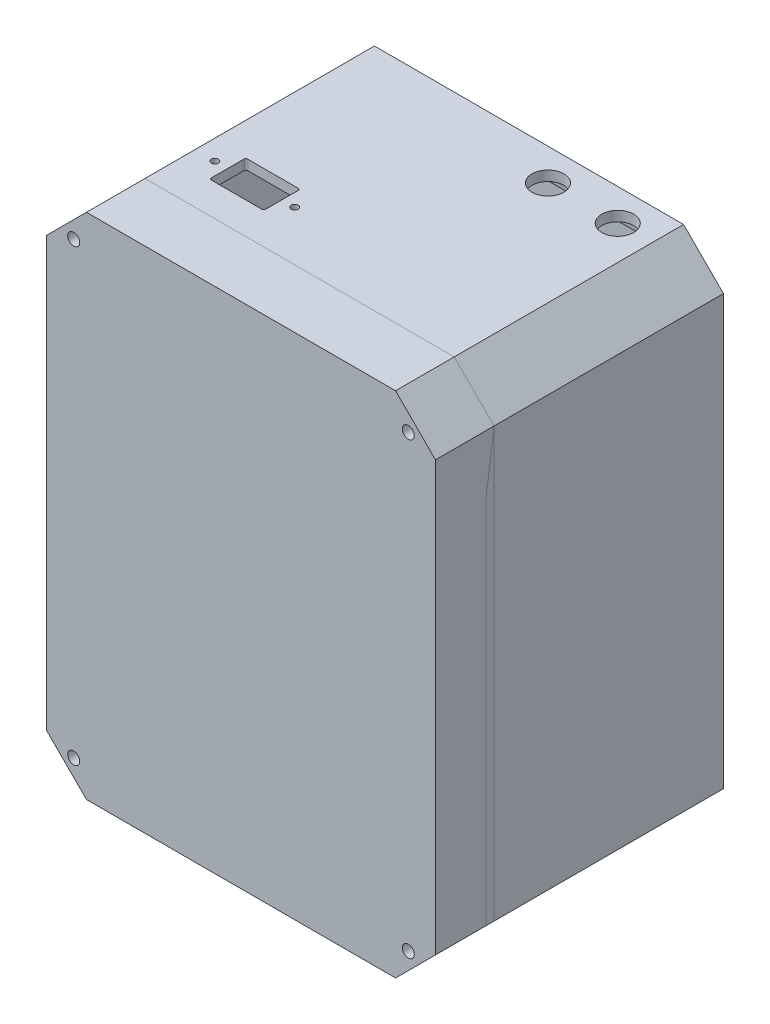
SolidWorks part; units mm, degrees
ref_plane "Front Plane" through (0, 0, 0) normal (1, 0, 0) x (0, 1, 0)
ref_plane "Top Plane" through (0, 0, 0) normal (0, 0, 1) x (0, 1, 0)
ref_plane "Right Plane" through (0, 0, 0) normal (0, 1, 0) x (-1, 0, 0)
sketch "Sketch1" plane through (0, 0, 0) normal (0, 0, 1) x (0, 1, 0)
  line L0 (-127.5, -25.5) -> (127.5, -25.5) construction
  line L1 (-107.5, 97.5) -> (107.5, 97.5)
  line L2 (-127.5, 77.5) -> (-127.5, -77.5)
  line L3 (-107.5, -97.5) -> (107.5, -97.5)
  line L4 (127.5, 77.5) -> (127.5, -77.5)
  line L5 (-127.5, 97.5) -> (127.5, -97.5) construction
  line L6 (-127.5, -97.5) -> (127.5, 97.5) construction
  line L7 (-127.5, -60.5) -> (127.5, -60.5) construction
  line L8 (-107.5, -18.875) -> (-107.5, -32.125) construction
  line L9 (-67.5, -53.875) -> (-67.5, -67.125) construction
  line L10 (-107.5, 97.5) -> (-127.5, 77.5)
  line L11 (107.5, 97.5) -> (127.5, 77.5)
  line L12 (127.5, -77.5) -> (107.5, -97.5)
  line L13 (-127.5, -77.5) -> (-107.5, -97.5)
  line L14 (-117.5, 87.5) -> (117.5, -87.5) construction
  line L15 (-112.6365, 83.8782) -> (112.6365, 83.8782) construction
  line L16 (-112.6365, 83.8782) -> (-112.6365, -83.8782) construction
  line L17 (-112.6365, -83.8782) -> (112.6365, -83.8782) construction
  line L18 (112.6365, 83.8782) -> (112.6365, -83.8782) construction
  line L19 (-112.6365, 83.8782) -> (112.6365, -83.8782) construction
  line L20 (-112.6365, -83.8782) -> (112.6365, 83.8782) construction
  circle A0 centre (-114.5, 44.5) radius 2.75 construction
  circle A1 centre (114.5, 44.5) radius 2.75 construction
  circle A2 centre (-107.5, -18.875) radius 2.75 construction
  circle A3 centre (-107.5, -32.125) radius 2.75 construction
  circle A4 centre (-67.5, -53.875) radius 2.75 construction
  circle A5 centre (-67.5, -67.125) radius 2.75 construction
  circle A6 centre (-112.6365, 83.8782) radius 2.1
  circle A7 centre (112.6365, 83.8782) radius 2.1
  circle A8 centre (112.6365, -83.8782) radius 2.1
  circle A9 centre (-112.6365, -83.8782) radius 2.1
  point P0 (0, 0)
  point P18 (-107.5, -25.5)
  point P19 (-67.5, -60.5)
  point P32 (0, 0)
  point P37 (-117.5, 87.5)
  point P41 (117.5, -87.5)
  dimension "D6" = 5.5
  dimension "D9" = 5.5
  dimension "D15" = 4.2
  dimension "D1" = 255
  dimension "D2" = 195
  dimension "D3" = 53
  dimension "D4" = 13
  dimension "D5" = 13
  dimension "D7" = 70
  dimension "D8" = 35
  dimension "D10" = 13.25
  dimension "D11" = 13.25
  dimension "D12" = 20
  dimension "D13" = 60
  dimension "D14" = 6
extrude "Boss-Extrude2" add sketch "Sketch1" along normal blind 115
shell "Shell1" thickness 5 removed face at (85.9782, 112.6365, 115)
sketch "Sketch9" plane through (0, 0, 5) normal (0, 0, 1) x (1, 0, 0)
  line L0 (-75.4289, -122.5) -> (75.4289, -122.5) construction
  line L1 (10.875, -122.5) -> (75.125, -122.5)
  line L2 (10.875, -122.5) -> (10.875, -22.5)
  line L3 (10.875, -22.5) -> (75.125, -22.5)
  line L4 (75.125, -122.5) -> (75.125, -22.5)
  dimension "D1" = 8
  dimension "D2" = 8
  dimension "D3" = 100
extrude "Boss-Extrude3" add sketch "Sketch9" along normal blind 2
sketch "Sketch10" plane through (0, 0, 5) normal (0, 0, 1) x (1, 0, 0)
  line L0 (75.125, -122.5) -> (75.125, -22.5) construction
  line L1 (10.875, -22.5) -> (75.125, -22.5)
  line L2 (10.875, -22.5) -> (10.875, 77.5)
  line L3 (10.875, 77.5) -> (75.125, 77.5)
  line L4 (75.125, -22.5) -> (75.125, 77.5)
  dimension "D1" = 100
extrude "Boss-Extrude4" add sketch "Sketch10" along normal blind 1
sketch "Sketch2" plane through (0, 0, 5) normal (0, 0, 1) x (1, 0, 0)
  circle A0 centre (53.875, -67.5) radius 2.75 construction
  circle A1 centre (67.125, -67.5) radius 2.75 construction
  circle A2 centre (32.125, -107.5) radius 2.75 construction
  circle A3 centre (18.875, -107.5) radius 2.75 construction
  circle A4 centre (-44.5, 114.5) radius 2.75 construction
  circle A5 centre (-44.5, -114.5) radius 2.75 construction
  circle A6 centre (53.875, -67.5) radius 2.75
  circle A7 centre (67.125, -67.5) radius 2.75
  circle A8 centre (32.125, -107.5) radius 2.75
  circle A9 centre (18.875, -107.5) radius 2.75
  circle A10 centre (-44.5, 114.5) radius 2.75
  circle A11 centre (-44.5, -114.5) radius 2.75
extrude "Cut-Extrude1" cut sketch "Sketch2" against normal through all both and the other way through all
sketch "Sketch3" plane through (0, -127.5, 0) normal (0, -1, 0) x (1, 0, 0)
  line L0 (-77.5, 0) -> (77.5, 0) construction
  line L1 (10.5, 0) -> (40.5, 0)
  line L2 (10.5, 0) -> (10.5, 65)
  line L3 (10.5, 65) -> (40.5, 65)
  line L4 (40.5, 0) -> (40.5, 65)
  line L6 (45.5, 0) -> (75.5, 0)
  line L7 (45.5, 0) -> (45.5, 65)
  line L8 (45.5, 65) -> (75.5, 65)
  line L9 (75.5, 0) -> (75.5, 65)
  point P10 (25.5, 0)
  point P11 (0, 0)
  point P13 (60.5, 0)
  point P14 (0, 0)
  dimension "D1" = 65
  dimension "D2" = 0
  dimension "D3" = 30
extrude "Cut-Extrude2" cut sketch "Sketch3" against normal up to surface (5 mm away) up to face at (21.5, -122.5, 33)
sketch "Sketch4" plane through (0, 127.5, 0) normal (0, 1, 0) x (-1, 0, 0)
  line L0 (-75.4289, 5) -> (75.4289, 5) construction
  circle A0 centre (-60.5, 16) radius 8
  circle A1 centre (-25.5, 16) radius 8
  point P4 (0, 0)
  point P6 (0, 0)
  point P8 (0, 0)
  dimension "D1" = 16
  dimension "D2" = 11
extrude "Cut-Extrude3" cut sketch "Sketch4" against normal up to next
chamfer "Chamfer2" distance 5 angle 45 4 edges at (-32.4645, -122.5, 5) (92.5, 0, 5) (0, 122.5, 5) (-92.5, 0, 5)
sketch "Sketch5" plane through (0, 127.5, 0) normal (0, 1, 0) x (-1, 0, 0)
  line L0 (27.5, 90) -> (67.5, 90) construction
  line L1 (34.9, 99.1) -> (60.1, 99.1)
  line L2 (33.9, 98.1) -> (33.9, 81.9)
  line L3 (34.9, 80.9) -> (60.1, 80.9)
  line L4 (61.1, 98.1) -> (61.1, 81.9)
  line L5 (33.9, 99.1) -> (61.1, 80.9) construction
  line L6 (33.9, 80.9) -> (61.1, 99.1) construction
  line L7 (-77.5, 115) -> (77.5, 115) construction
  line L8 (97.5, 115) -> (97.5, 0) construction
  circle A0 centre (27.5, 90) radius 1.75
  circle A1 centre (67.5, 90) radius 1.75
  arc A2 (33.9, 81.9) -> (34.9, 80.9) centre (34.9, 81.9) ccw
  arc A3 (60.1, 80.9) -> (61.1, 81.9) centre (60.1, 81.9) ccw
  arc A4 (61.1, 98.1) -> (60.1, 99.1) centre (60.1, 98.1) ccw
  arc A5 (34.9, 99.1) -> (33.9, 98.1) centre (34.9, 98.1) ccw
  point P0 (47.5, 90)
  point P7 (47.5, 90)
  dimension "D4" = 3.5
  dimension "D5" = 1
  dimension "D1" = 27.2
  dimension "D2" = 18.2
  dimension "D3" = 40
  dimension "D6" = 25
  dimension "D7" = 50
extrude "Cut-Extrude4" cut sketch "Sketch5" against normal up to next
sketch "Sketch6" plane through (0, 0, 5) normal (0, 0, 1) x (1, 0, 0)
  line L0 (10.5, -122.5) -> (-75.4289, -122.5) construction
  line L1 (-62, -122.5) -> (-27, -122.5)
  line L2 (-62, -122.5) -> (-62, 122.5)
  line L3 (-62, 122.5) -> (-27, 122.5)
  line L4 (-27, -122.5) -> (-27, 122.5)
  line L5 (75.4289, 122.5) -> (-75.4289, 122.5) construction
  point P8 (-44.5, -122.5)
  point P9 (-44.5, 122.5)
  point P10 (0, 0)
  dimension "D1" = 180
  dimension "D2" = 35
extrude "Cut-Extrude5" cut sketch "Sketch6" along normal through all
sketch "Sketch7" plane through (0, 122.5, 0) normal (0, -1, 0) x (1, 0, 0)
  line L0 (77.5, 0) -> (-77.5, 0) construction
  line L1 (-27, 5) -> (-62, 5) construction
  line L2 (25.5, 5) -> (35.0263, 10.5)
  line L3 (35.0263, 10.5) -> (35.0263, 21.5)
  line L4 (35.0263, 21.5) -> (25.5, 27)
  line L5 (25.5, 27) -> (15.9737, 21.5)
  line L6 (15.9737, 21.5) -> (15.9737, 10.5)
  line L7 (15.9737, 10.5) -> (25.5, 5)
  line L8 (60.5, 5) -> (70.0263, 10.5)
  line L9 (70.0263, 10.5) -> (70.0263, 21.5)
  line L10 (70.0263, 21.5) -> (60.5, 27)
  line L11 (60.5, 27) -> (50.9737, 21.5)
  line L12 (50.9737, 21.5) -> (50.9737, 10.5)
  line L13 (50.9737, 10.5) -> (60.5, 5)
  circle A2 centre (25.5, 16) radius 9.5263 construction
  circle A3 centre (60.5, 16) radius 9.5263 construction
  point P2 (0, 0)
  point P5 (0, 0)
  point P22 (0, 0)
  point P23 (0, 0)
  dimension "D1" = 0
extrude "Cut-Extrude6" cut sketch "Sketch7" along normal up to next
sketch "Sketch11" plane through (0, 0, 115) normal (0, 0, 1) x (1, 0, 0)
  line L8 (-97.5, -107.5) -> (-77.5, -127.5)
  line L9 (-77.5, -127.5) -> (77.5, -127.5)
  line L10 (77.5, -127.5) -> (97.5, -107.5)
  line L11 (97.5, -107.5) -> (97.5, 107.5)
  line L12 (97.5, 107.5) -> (77.5, 127.5)
  line L13 (77.5, 127.5) -> (-77.5, 127.5)
  line L14 (-77.5, 127.5) -> (-97.5, 107.5)
  line L15 (-97.5, 107.5) -> (-97.5, -107.5)
  line L16 (-97.5, -107.5) -> (-77.5, -127.5)
  line L17 (-77.5, -127.5) -> (77.5, -127.5)
  line L18 (77.5, -127.5) -> (97.5, -107.5)
  line L19 (97.5, -107.5) -> (97.5, 107.5)
  line L20 (97.5, 107.5) -> (77.5, 127.5)
  line L21 (77.5, 127.5) -> (-77.5, 127.5)
  line L22 (-77.5, 127.5) -> (-97.5, 107.5)
  line L23 (-97.5, 107.5) -> (-97.5, -107.5)
  circle A0 centre (83.8782, 112.6365) radius 2.75
  circle A1 centre (83.8782, -112.6365) radius 2.75
  circle A2 centre (-83.8782, -112.6365) radius 2.75
  circle A3 centre (-83.8782, 112.6365) radius 2.75
  dimension "D2" = 5.5
  dimension "D1" = 0
extrude "Boss-Extrude5" add sketch "Sketch11" along normal blind 4 separate body
sketch "Sketch12" plane through (0, 0, 115) normal (0, 0, -1) x (1, 0, 0)
  line L0 (-88.5, 102.5444) -> (-88.5, 102.5444)
  line L1 (-88.5, 102.5444) -> (-88.5, -102.5444)
  line L2 (-88.5, -102.5444) -> (-88.5, -102.5444)
  line L3 (-74.2001, -118.0719) -> (-73.7721, -118.5)
  line L4 (-73.7721, -118.5) -> (73.7721, -118.5)
  line L5 (73.7721, -118.5) -> (74.2001, -118.0719)
  line L6 (88.5, -102.5444) -> (88.5, -102.5444)
  line L7 (88.5, -102.5444) -> (88.5, 102.5444)
  line L40 (88.5, 102.5444) -> (88.5, 102.5444)
  line L41 (74.2001, 118.0719) -> (73.7721, 118.5)
  line L42 (73.7721, 118.5) -> (-73.7721, 118.5)
  line L43 (-73.7721, 118.5) -> (-74.2001, 118.0719)
  line L44 (-89.5558, 108.3732) -> (-92.5, 105.4289)
  line L45 (-92.5, 105.4289) -> (-92.5, -105.4289)
  line L46 (-92.5, -105.4289) -> (-89.5558, -108.3732)
  line L47 (-79.6149, -118.314) -> (-75.4289, -122.5)
  line L48 (-75.4289, -122.5) -> (75.4289, -122.5)
  line L49 (75.4289, -122.5) -> (79.6149, -118.314)
  line L50 (89.5558, -108.3732) -> (92.5, -105.4289)
  line L51 (92.5, -105.4289) -> (92.5, 105.4289)
  line L52 (92.5, 105.4289) -> (89.5558, 108.3732)
  line L53 (79.6149, 118.314) -> (75.4289, 122.5)
  line L54 (75.4289, 122.5) -> (-75.4289, 122.5)
  line L55 (-75.4289, 122.5) -> (-79.6149, 118.314)
  line L56 (-89.5558, 108.3732) -> (-92.5, 105.4289)
  line L57 (-92.5, 105.4289) -> (-92.5, -105.4289)
  line L58 (-92.5, -105.4289) -> (-89.5558, -108.3732)
  line L59 (-79.6149, -118.314) -> (-75.4289, -122.5)
  line L60 (-75.4289, -122.5) -> (75.4289, -122.5)
  line L61 (75.4289, -122.5) -> (79.6149, -118.314)
  line L62 (89.5558, -108.3732) -> (92.5, -105.4289)
  line L63 (92.5, -105.4289) -> (92.5, 105.4289)
  line L64 (92.5, 105.4289) -> (89.5558, 108.3732)
  line L65 (79.6149, 118.314) -> (75.4289, 122.5)
  line L66 (75.4289, 122.5) -> (-75.4289, 122.5)
  line L67 (-75.4289, 122.5) -> (-79.6149, 118.314)
  arc A0 (-74.2001, -118.0719) -> (-88.5, -102.5444) centre (-83.8782, -112.6365) ccw
  arc A1 (88.5, -102.5444) -> (74.2001, -118.0719) centre (83.8782, -112.6365) ccw
  arc A3 (74.2001, 118.0719) -> (88.5, 102.5444) centre (83.8782, 112.6365) ccw
  arc A5 (-88.5, 102.5444) -> (-74.2001, 118.0719) centre (-83.8782, 112.6365) ccw
  arc A12 (-79.6149, -118.314) -> (-89.5558, -108.3732) centre (-83.8782, -112.6365) ccw
  arc A13 (89.5558, -108.3732) -> (79.6149, -118.314) centre (83.8782, -112.6365) ccw
  arc A14 (79.6149, 118.314) -> (89.5558, 108.3732) centre (83.8782, 112.6365) ccw
  arc A15 (-89.5558, 108.3732) -> (-79.6149, 118.314) centre (-83.8782, 112.6365) ccw
  arc A16 (-79.6149, -118.314) -> (-89.5558, -108.3732) centre (-83.8782, -112.6365) ccw
  arc A17 (89.5558, -108.3732) -> (79.6149, -118.314) centre (83.8782, -112.6365) ccw
  arc A18 (79.6149, 118.314) -> (89.5558, 108.3732) centre (83.8782, 112.6365) ccw
  arc A19 (-89.5558, 108.3732) -> (-79.6149, 118.314) centre (-83.8782, 112.6365) ccw
  dimension "D1" = 4
  dimension "D7" = 0
extrude "Boss-Extrude6" add sketch "Sketch12" along normal blind 5
sketch "Sketch13" plane through (0, 0, 115) normal (0, 0, 1) x (1, 0, 0)
  line L0 (88.5, 102.5444) -> (88.5, 102.5444)
  line L1 (74.2001, 118.0719) -> (73.7721, 118.5)
  line L2 (73.7721, 118.5) -> (-73.7721, 118.5)
  line L3 (-73.7721, 118.5) -> (-74.2001, 118.0719)
  line L4 (-88.5, 102.5444) -> (-88.5, 102.5444)
  line L5 (-88.5, 102.5444) -> (-88.5, -102.5444)
  line L6 (-88.5, -102.5444) -> (-88.5, -102.5444)
  line L7 (-74.2001, -118.0719) -> (-73.7721, -118.5)
  line L8 (-97.5, -107.5) -> (-77.5, -127.5)
  line L9 (-77.5, -127.5) -> (77.5, -127.5)
  line L10 (77.5, -127.5) -> (97.5, -107.5)
  line L11 (97.5, -107.5) -> (97.5, 107.5)
  line L12 (97.5, 107.5) -> (77.5, 127.5)
  line L13 (77.5, 127.5) -> (-77.5, 127.5)
  line L14 (-77.5, 127.5) -> (-97.5, 107.5)
  line L15 (-97.5, 107.5) -> (-97.5, -107.5)
  line L16 (-97.5, -107.5) -> (-77.5, -127.5)
  line L17 (-77.5, -127.5) -> (77.5, -127.5)
  line L18 (77.5, -127.5) -> (97.5, -107.5)
  line L19 (97.5, -107.5) -> (97.5, 107.5)
  line L20 (97.5, 107.5) -> (77.5, 127.5)
  line L21 (77.5, 127.5) -> (-77.5, 127.5)
  line L22 (-77.5, 127.5) -> (-97.5, 107.5)
  line L23 (-97.5, 107.5) -> (-97.5, -107.5)
  line L24 (-73.7721, -118.5) -> (73.7721, -118.5)
  line L25 (73.7721, -118.5) -> (74.2001, -118.0719)
  line L26 (88.5, -102.5444) -> (88.5, -102.5444)
  line L27 (88.5, -102.5444) -> (88.5, 102.5444)
  line L28 (-92.5, -105.4289) -> (-89.5558, -108.3732)
  line L29 (-92.5, 105.4289) -> (-92.5, -105.4289)
  line L30 (-89.5558, 108.3732) -> (-92.5, 105.4289)
  line L31 (-75.4289, 122.5) -> (-79.6149, 118.314)
  line L32 (75.4289, 122.5) -> (-75.4289, 122.5)
  line L33 (79.6149, 118.314) -> (75.4289, 122.5)
  line L34 (92.5, 105.4289) -> (89.5558, 108.3732)
  line L35 (92.5, -105.4289) -> (92.5, 105.4289)
  line L36 (89.5558, -108.3732) -> (92.5, -105.4289)
  line L37 (75.4289, -122.5) -> (79.6149, -118.314)
  line L38 (-75.4289, -122.5) -> (75.4289, -122.5)
  line L39 (-79.6149, -118.314) -> (-75.4289, -122.5)
  line L40 (-92.5, -105.4289) -> (-89.5558, -108.3732)
  line L41 (-92.5, 105.4289) -> (-92.5, -105.4289)
  line L42 (-89.5558, 108.3732) -> (-92.5, 105.4289)
  line L43 (-75.4289, 122.5) -> (-79.6149, 118.314)
  line L44 (75.4289, 122.5) -> (-75.4289, 122.5)
  line L45 (79.6149, 118.314) -> (75.4289, 122.5)
  line L46 (92.5, 105.4289) -> (89.5558, 108.3732)
  line L47 (92.5, -105.4289) -> (92.5, 105.4289)
  line L48 (89.5558, -108.3732) -> (92.5, -105.4289)
  line L49 (75.4289, -122.5) -> (79.6149, -118.314)
  line L50 (-75.4289, -122.5) -> (75.4289, -122.5)
  line L51 (-79.6149, -118.314) -> (-75.4289, -122.5)
  circle A0 centre (83.8782, 112.6365) radius 3
  circle A1 centre (83.8782, -112.6365) radius 3
  circle A2 centre (-83.8782, -112.6365) radius 3
  circle A3 centre (-83.8782, 112.6365) radius 3
  arc A4 (-89.5558, 108.3732) -> (-79.6149, 118.314) centre (-83.8782, 112.6365) ccw
  arc A5 (79.6149, 118.314) -> (89.5558, 108.3732) centre (83.8782, 112.6365) ccw
  arc A6 (89.5558, -108.3732) -> (79.6149, -118.314) centre (83.8782, -112.6365) ccw
  arc A7 (-79.6149, -118.314) -> (-89.5558, -108.3732) centre (-83.8782, -112.6365) ccw
  arc A8 (-89.5558, 108.3732) -> (-79.6149, 118.314) centre (-83.8782, 112.6365) ccw
  arc A9 (79.6149, 118.314) -> (89.5558, 108.3732) centre (83.8782, 112.6365) ccw
  arc A10 (89.5558, -108.3732) -> (79.6149, -118.314) centre (83.8782, -112.6365) ccw
  arc A11 (-79.6149, -118.314) -> (-89.5558, -108.3732) centre (-83.8782, -112.6365) ccw
  arc A12 (74.2001, 118.0719) -> (88.5, 102.5444) centre (83.8782, 112.6365) ccw
  arc A13 (-88.5, 102.5444) -> (-74.2001, 118.0719) centre (-83.8782, 112.6365) ccw
  arc A14 (-74.2001, -118.0719) -> (-88.5, -102.5444) centre (-83.8782, -112.6365) ccw
  arc A15 (88.5, -102.5444) -> (74.2001, -118.0719) centre (83.8782, -112.6365) ccw
  line M25 (-89.5558, -108.3732) -> (-92.5, -105.4289)
  line M26 (-92.5, -105.4289) -> (-92.5, 105.4289)
  line M27 (-92.5, 105.4289) -> (-89.5558, 108.3732)
  arc M28 (-89.5558, 108.3732) -> (-79.6149, 118.314) centre (-83.8782, 112.6365) ccw
  line M29 (-79.6149, 118.314) -> (-75.4289, 122.5)
  line M30 (-75.4289, 122.5) -> (75.4289, 122.5)
  line M31 (75.4289, 122.5) -> (79.6149, 118.314)
  arc M32 (79.6149, 118.314) -> (89.5558, 108.3732) centre (83.8782, 112.6365) ccw
  line M33 (89.5558, 108.3732) -> (92.5, 105.4289)
  line M34 (92.5, 105.4289) -> (92.5, -105.4289)
  line M35 (92.5, -105.4289) -> (89.5558, -108.3732)
  arc M36 (89.5558, -108.3732) -> (79.6149, -118.314) centre (83.8782, -112.6365) ccw
  line M37 (79.6149, -118.314) -> (75.4289, -122.5)
  line M38 (75.4289, -122.5) -> (-75.4289, -122.5)
  line M39 (-75.4289, -122.5) -> (-79.6149, -118.314)
  arc M40 (-79.6149, -118.314) -> (-89.5558, -108.3732) centre (-83.8782, -112.6365) ccw
  line M43 (-97.5, -107.5) -> (-77.5, -127.5)
  line M44 (-77.5, -127.5) -> (77.5, -127.5)
  line M45 (77.5, -127.5) -> (97.5, -107.5)
  line M46 (97.5, -107.5) -> (97.5, 107.5)
  line M47 (97.5, 107.5) -> (77.5, 127.5)
  line M48 (77.5, 127.5) -> (-77.5, 127.5)
  line M49 (-77.5, 127.5) -> (-97.5, 107.5)
  line M50 (-97.5, 107.5) -> (-97.5, -107.5)
  dimension "D3" = 6
  dimension "D1" = 0
  dimension "D2" = 0
  dimension "D4" = 4
extrude "Boss-Extrude7" add sketch "Sketch13" against normal blind 4 separate body contours L27 A15 L25 L24 L7 A14 L5 A13 L3 L2 L1 A12 M25 M40 M39 M38 M37 M36 M35 M34 M33 M32 M31 M30 M29 M28 M27 M26 region at (-89.43, 0, 115)
extrude "Boss-Extrude8" add sketch "Sketch13<4>" along normal blind 25.4 contours A3 A2 A1 A0 M50 M43 M44 M45 M46 M47 M48 M49 M40 M25 M26 M27 M28 M29 M30 M31 M32 M33 M34 M35 M36 M37 M38 M39 | L27 A15 L25 L24 L7 A14 L5 A13 L3 L2 L1 A12 M25 M40 M39 M38 M37 M36 M35 M34 M33 M32 M31 M30 M29 M28 M27 M26 region at (-94.2899, 0, 115) region at (-89.43, 0, 115)
sketch "Sketch13<4>" plane through (0, 0, 115) normal (0, 0, 1) x (1, 0, 0) same geometry as "Sketch13"
sketch "Sketch14" plane through (0, 0, 140.4) normal (0, 0, 1) x (1, 0, 0)
  line L8 (-97.5, 107.5) -> (-97.5, -107.5)
  line L9 (-97.5, -107.5) -> (-77.5, -127.5)
  line L10 (-77.5, -127.5) -> (77.5, -127.5)
  line L11 (77.5, -127.5) -> (97.5, -107.5)
  line L12 (97.5, -107.5) -> (97.5, 107.5)
  line L13 (97.5, 107.5) -> (77.5, 127.5)
  line L14 (77.5, 127.5) -> (-77.5, 127.5)
  line L15 (-77.5, 127.5) -> (-97.5, 107.5)
  line L16 (-97.5, 107.5) -> (-97.5, -107.5)
  line L17 (-97.5, -107.5) -> (-77.5, -127.5)
  line L18 (-77.5, -127.5) -> (77.5, -127.5)
  line L19 (77.5, -127.5) -> (97.5, -107.5)
  line L20 (97.5, -107.5) -> (97.5, 107.5)
  line L21 (97.5, 107.5) -> (77.5, 127.5)
  line L22 (77.5, 127.5) -> (-77.5, 127.5)
  line L23 (-77.5, 127.5) -> (-97.5, 107.5)
  circle A1 centre (-83.8782, 112.6365) radius 3
  circle A2 centre (-83.8782, 112.6365) radius 3
  circle A3 centre (-83.8782, -112.6365) radius 3
  circle A4 centre (-83.8782, -112.6365) radius 3
  circle A5 centre (83.8782, -112.6365) radius 3
  circle A6 centre (83.8782, -112.6365) radius 3
  circle A7 centre (83.8782, 112.6365) radius 3
  circle A8 centre (83.8782, 112.6365) radius 3
  dimension "D1" = 0
  dimension "D2" = 0
  dimension "D3" = 0
  dimension "D4" = 0
  dimension "D5" = 0
extrude "Boss-Extrude9" add sketch "Sketch14" along normal blind 4
equation "\"WallThickness\"= 5"
equation "\"D1@Sketch1\"=\"WallThickness\"+250"
equation "\"D2@Sketch1\"=\"WallThickness\"+190"
equation "\"D1@Shell1\"=\"WallThickness\""
equation "\"D14@Sketch1\"=\"WallThickness\"+1"
